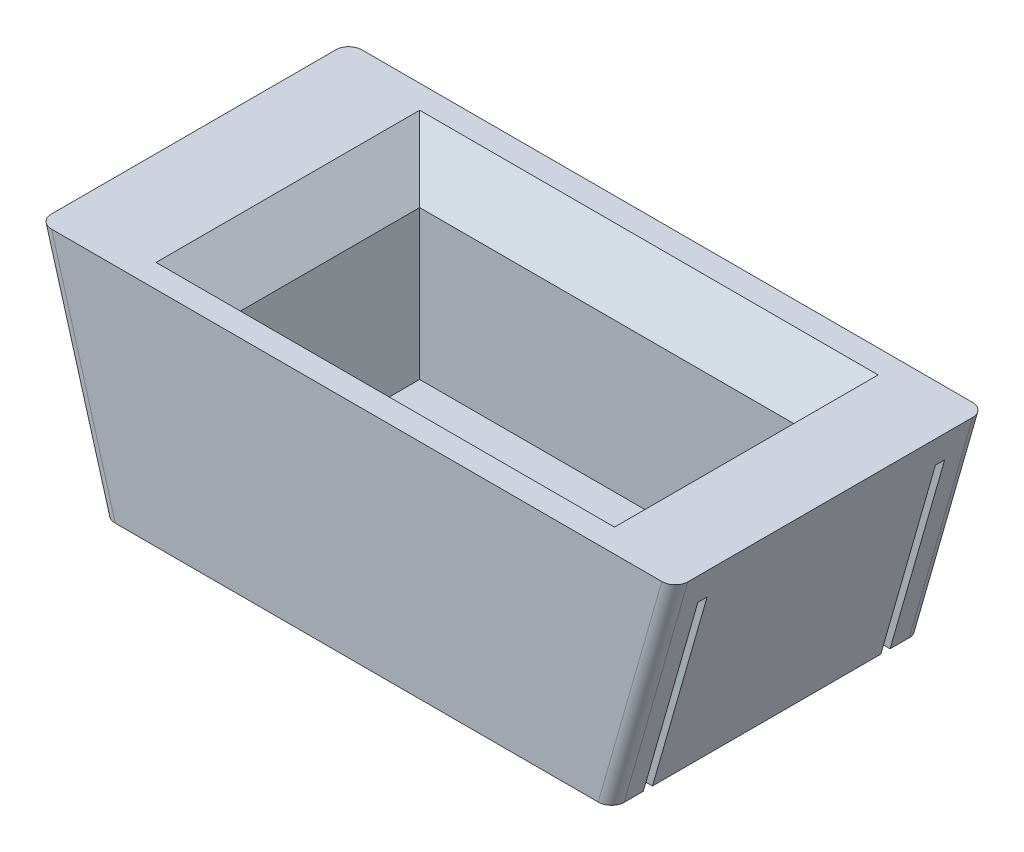
SolidWorks part; units mm, degrees
ref_plane "Front" through (0, 0, 0) normal (0, 0, 1) x (1, 0, 0)
ref_plane "Top" through (0, 0, 0) normal (0, 1, 0) x (1, 0, 0)
ref_plane "Right" through (0, 0, 0) normal (1, 0, 0) x (0, 0, -1)
sketch "Sketch1" plane through (0, 0, 0) normal (0, 1, 0) x (1, 0, 0)
  line L1 (-63.5, -24.6126) -> (63.5, -24.6126)
  line L2 (-63.5, -24.6126) -> (-63.5, 24.6126)
  line L3 (-63.5, 24.6126) -> (63.5, 24.6126)
  line L4 (63.5, -24.6126) -> (63.5, 24.6126)
  line L5 (0, 24.6126) -> (0, -24.6126) construction
  line L6 (-63.5, 0) -> (63.5, 0) construction
  line L7 (-63.5, -22.7711) -> (63.5, -22.7711)
  line L8 (-63.5, -22.7711) -> (-63.5, 22.7711)
  line L9 (-63.5, 22.7711) -> (63.5, 22.7711)
  line L10 (63.5, -22.7711) -> (63.5, 22.7711)
  line L11 (0, 22.7711) -> (0, -22.7711) construction
  line L12 (-63.5, 0) -> (63.5, 0) construction
  line L13 (-63.5, -30.9626) -> (63.5, -30.9626)
  line L14 (-63.5, -30.9626) -> (-63.5, 30.9626)
  line L15 (-63.5, 30.9626) -> (63.5, 30.9626)
  line L16 (63.5, -30.9626) -> (63.5, 30.9626)
  line L17 (0, 30.9626) -> (0, -30.9626) construction
  line L18 (-63.5, 0) -> (63.5, 0) construction
  point P0 (0, 0)
  point P4 (0, 0)
  point P8 (0, 0)
  dimension "D1" = 49.2252
  dimension "D2" = 127
  dimension "D3" = 1.8415
  dimension "D4" = 6.35
extrude "Boss-Extrude1" add sketch "Sketch1" along normal blind 44.45 contours L3 L16 L15 L14 | L13 L16 L1 L14 | L3 L4 L1 L2 region at (0, 0, 27.7876) region at (0, 0, -27.7876)
extrude "Cut-Extrude2" cut sketch "Sketch1<3>" along normal blind 38.1 contours L2 L9 L4 L3 | L7 L2 L1 L4 region at (0, 0, 23.6919) region at (0, 0, -23.6919)
sketch "Sketch1<3>" plane through (0, 0, 0) normal (0, 1, 0) x (1, 0, 0) same geometry as "Sketch1"
sketch "Sketch2" plane through (0, 44.45, 0) normal (0, 1, 0) x (1, 0, 0)
  line L0 (63.5, -30.9626) -> (63.5, 30.9626) construction
  line L1 (-34.544, -16.129) -> (36.576, -16.129)
  line L3 (-34.544, 16.129) -> (36.576, 16.129)
  line L4 (36.576, -16.129) -> (36.576, 16.129)
  line L5 (1.016, 16.129) -> (1.016, -16.129) construction
  line L6 (-34.544, 0) -> (36.576, 0) construction
  line L11 (1.016, 12.7) -> (1.016, -12.7) construction
  line L12 (-20.32, 0) -> (20.32, 0) construction
  line L13 (-5.2166, -11.5914) -> (30.226, -11.5914)
  line L14 (-5.2166, -11.5914) -> (-5.2166, 11.5914)
  line L15 (-5.2166, 11.5914) -> (30.226, 11.5914)
  line L16 (30.226, -11.5914) -> (30.226, 11.5914)
  line L17 (12.5047, 11.5914) -> (12.5047, -11.5914) construction
  line L18 (-5.2166, 0) -> (30.226, 0) construction
  line L19 (-34.544, 16.129) -> (-34.544, -16.129)
  line L20 (-63.5, -30.9626) -> (63.5, -30.9626) construction
  point P0 (0, 0)
  point P4 (1.016, 0)
  point P5 (12.5047, 0)
  dimension "D1" = 32.258
  dimension "D3" = 6.35
  dimension "D4" = 35.4426
  dimension "D5" = 23.1828
  dimension "D6" = 71.12
  dimension "D7" = 26.924
  dimension "D8" = 14.8336
extrude "Cut-Extrude3" cut sketch "Sketch2" against normal blind 38.1
chamfer "Chamfer2" distance 10.16 angle 45 4 edges at (1.016, 44.45, 16.129) (1.016, 44.45, -16.129) (36.576, 44.45, 0) (-34.544, 44.45, 0)
sketch "Sketch7" plane through (0, 0, 30.9626) normal (0, 0, 1) x (1, 0, 0)
  line L0 (-63.5, 44.45) -> (-63.5, 0)
  line L1 (-63.5, 44.45) -> (63.5, 44.45) construction
  line L2 (-63.5, 44.45) -> (-63.5, 0) construction
  line L3 (-63.5, 0) -> (63.5, 0) construction
  line L4 (63.5, 44.45) -> (63.5, 0) construction
  line L7 (-63.5, 0) -> (-50.7955, 0)
  line L8 (-50.7955, 0) -> (-63.5, 44.45)
  line L9 (0, 0) -> (0, 44.45)
  line L10 (63.5, 0) -> (50.7955, 0)
  line L11 (63.5, 44.45) -> (63.5, 0)
  line L12 (50.7955, 0) -> (63.5, 44.45)
  point P4 (0, 22.225)
  point P12 (0, 22.225)
  line M13 (-63.5, 0) -> (63.5, 0)
  line M18 (63.5, 0) -> (63.5, 44.45)
  line M19 (-63.5, 44.45) -> (-63.5, 0)
extrude "Cut-Extrude5" cut sketch "Sketch7" against normal through all contours L8 M13 M19 | L12 M13 M18 region at (-59.2652, 14.8167, 30.9626) region at (59.2652, 14.8167, 30.9626)
fillet "Fillet3" radius 2.54 4 edges at (-57.1477, 22.225, 30.9626) (-57.1477, 22.225, -30.9626) (57.1477, 22.225, -30.9626) (57.1477, 22.225, 30.9626)
extrude "Cut-Extrude6" cut sketch "Sketch2<3>" against normal through all contours L15 L16 L13 L14
sketch "Sketch2<3>" plane through (0, 44.45, 0) normal (0, 1, 0) x (1, 0, 0) same geometry as "Sketch2"
chamfer "Chamfer3" distance 2.54 angle 45 4 edges at (12.5047, 0, 11.5914) (-5.2166, 0, 0) (30.226, 0, 0) (12.5047, 0, -11.5914)
sketch "Sketch9" plane through (0, 44.45, 0) normal (0, 1, 0) x (1, 0, 0)
  line L0 (46.736, -26.289) -> (36.576, -16.129) construction
  line L1 (-34.544, 16.129) -> (36.576, 16.129) construction
  line L2 (-34.544, 16.129) -> (-34.544, -16.129) construction
  line L3 (-34.544, -16.129) -> (36.576, -16.129) construction
  line L4 (36.576, 16.129) -> (36.576, -16.129) construction
  line L5 (-34.544, -16.129) -> (36.576, -16.129) construction
  line L6 (-36.294, 17.879) -> (-36.294, -17.879)
  line L7 (-36.294, -17.879) -> (38.326, -17.879)
  line L8 (38.326, 17.879) -> (38.326, -17.879)
  line L9 (-36.294, 17.879) -> (38.326, 17.879)
  dimension "D1" = 1.75
extrude "Cut-Extrude7" cut sketch "Sketch9" against normal up to surface (38.1 mm away) up to face at (12.5047, 6.35, 0)
